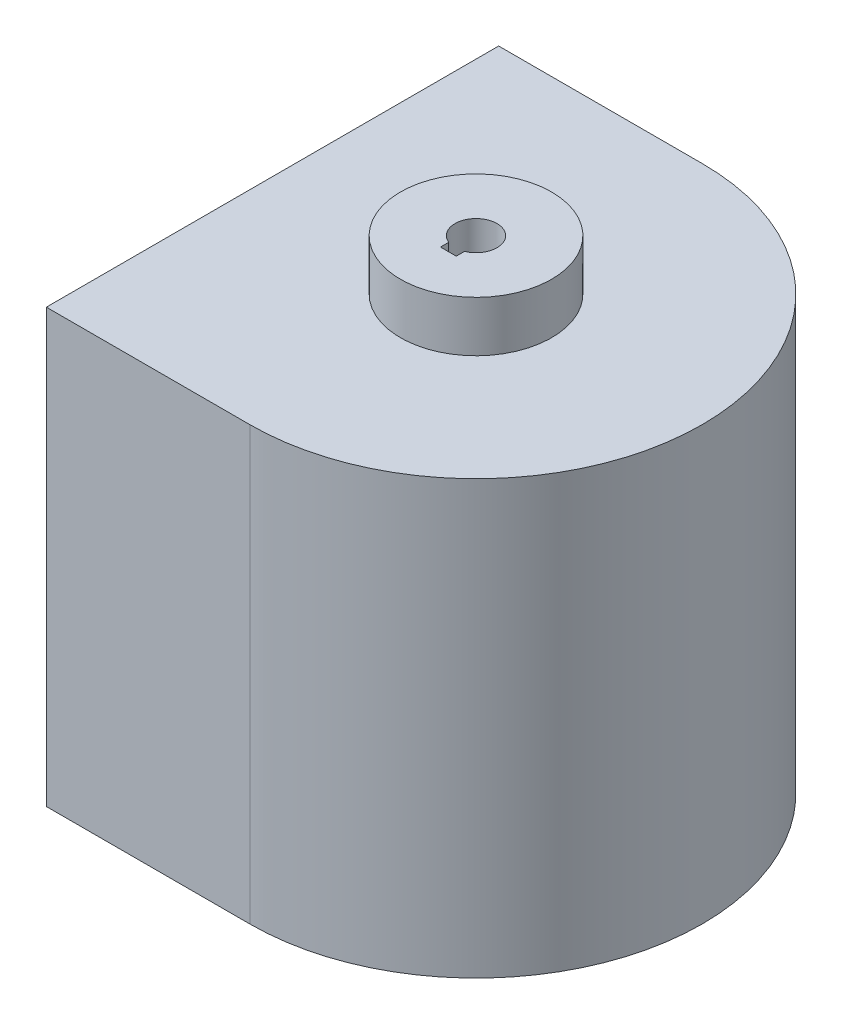
SolidWorks part; units mm, degrees
ref_plane "Front Plane" through (0, 0, 0) normal (0, 0, 1) x (1, 0, 0)
ref_plane "Top Plane" through (0, 0, 0) normal (0, 1, 0) x (1, 0, 0)
ref_plane "Right Plane" through (0, 0, 0) normal (1, 0, 0) x (0, 0, -1)
sketch "Sketch1" plane through (0, 0, 0) normal (0, 1, 0) x (1, 0, 0)
  line L0 (0, 44.45) -> (-40, 44.45)
  line L1 (-40, 44.45) -> (-40, -44.45)
  line L2 (-40, -44.45) -> (0, -44.45)
  arc A0 (0, 44.45) -> (0, -44.45) centre (0, 0) cw
  dimension "D1" = 44.45
  dimension "D2" = 40
extrude "Boss-Extrude1" add sketch "Sketch1" along normal blind 85
sketch "Sketch2" plane through (0, 85, 0) normal (0, 1, 0) x (1, 0, 0)
  circle A0 centre (0, 0) radius 14.86
sketch "Sketch3" plane through (0, 0, 0) normal (0, -1, 0) x (1, 0, 0)
  circle A0 centre (0, 0) radius 14.86
extrude "Boss-Extrude2" add sketch "Sketch2" along normal blind 9.95
extrude "Boss-Extrude3" add sketch "Sketch3" along normal blind 9.95
sketch "Sketch6" plane through (0, 94.95, 0) normal (0, 1, 0) x (1, 0, 0)
  line L5 (0, -4.12) -> (0, -5.44)
  line L6 (0, -5.44) -> (-1.55, -5.44)
  line L7 (0, -5.44) -> (1.55, -5.44)
  line L8 (-1.55, -5.44) -> (-1.55, -3.8173)
  line L9 (1.55, -5.44) -> (1.55, -3.8173)
  circle A1 centre (0, 0) radius 4.12
extrude "Cut-Extrude2" cut sketch "Sketch6" against normal blind 30 contours A1 | A1 L5 L7 L9 | A1 L8 L6 L5 region at (0.8023, 94.95, 4.7275) region at (-0.8023, 94.95, 4.7275) region at (0, 94.95, 0)
